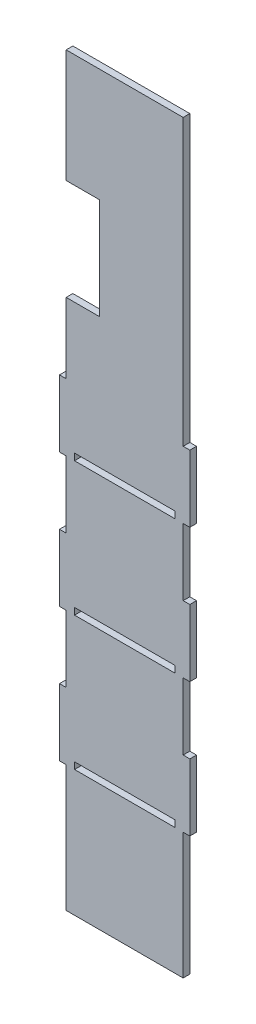
SolidWorks part; units mm, degrees
ref_plane "前视基准面" through (0, 0, 0) normal (0, 0, 1) x (1, 0, 0)
ref_plane "上视基准面" through (0, 0, 0) normal (0, 1, 0) x (1, 0, 0)
ref_plane "右视基准面" through (0, 0, 0) normal (1, 0, 0) x (0, 0, -1)
sketch "草图1" plane through (0, 0, 0) normal (0, 0, 1) x (1, 0, 0)
  line L38 (-8, 15.141) -> (-8, 49)
  line L39 (-8, 49) -> (27, 49)
  line L41 (-8, -15.141) -> (-8, -36.2215)
  line L42 (-8, -36.2215) -> (-10, -36.2215)
  line L43 (-10, -36.2215) -> (-10, -56.2215)
  line L44 (-10, -56.2215) -> (-8, -56.2215)
  line L45 (-8, -56.2215) -> (-8, -76.2215)
  line L46 (-8, -76.2215) -> (-10, -76.2215)
  line L47 (-10, -76.2215) -> (-10, -96.2215)
  line L48 (-10, -96.2215) -> (-8, -96.2215)
  line L49 (-8, -96.2215) -> (-8, -116.2215)
  line L52 (-8, -116.2215) -> (-10, -116.2215)
  line L53 (-10, -116.2215) -> (-10, -136.2215)
  line L54 (-10, -136.2215) -> (-8, -136.2215)
  line L55 (-8, -136.2215) -> (-8, -174)
  line L56 (-8, -174) -> (27, -174)
  line L58 (-8, -15.141) -> (2, -15.141)
  line L59 (2, -15.141) -> (2, 15.141)
  line L60 (2, 15.141) -> (-8, 15.141)
  line L61 (27, -136.2215) -> (27, -174)
  line L62 (29, -36.2215) -> (29, -56.2215)
  line L63 (29, -56.2215) -> (27, -56.2215)
  line L64 (27, -56.2215) -> (27, -76.2215)
  line L65 (27, -76.2215) -> (29, -76.2215)
  line L66 (29, -76.2215) -> (29, -96.2215)
  line L67 (29, -96.2215) -> (27, -96.2215)
  line L68 (27, -96.2215) -> (27, -116.2215)
  line L69 (29, -116.2215) -> (29, -136.2215)
  line L70 (29, -136.2215) -> (27, -136.2215)
  line L71 (27, -116.2215) -> (29, -116.2215)
  line L72 (27, 49) -> (27, -36.2215)
  line L73 (27, -36.2215) -> (29, -36.2215)
  line L83 (-5.5, -94.2215) -> (-5.5, -96.2215)
  line L84 (-5.5, -96.2215) -> (24.5, -96.2215)
  line L85 (24.5, -96.2215) -> (24.5, -94.2215)
  line L86 (24.5, -94.2215) -> (-5.5, -94.2215)
  line L87 (-5.5, -134.2215) -> (-5.5, -136.2215)
  line L88 (-5.5, -136.2215) -> (24.5, -136.2215)
  line L89 (24.5, -136.2215) -> (24.5, -134.2215)
  line L90 (24.5, -134.2215) -> (-5.5, -134.2215)
  line L91 (-5.5, -56.2215) -> (-5.5, -54.2215)
  line L92 (-5.5, -56.2215) -> (24.5, -56.2215)
  line L93 (-5.5, -54.2215) -> (24.5, -54.2215)
  line L94 (24.5, -54.2215) -> (24.5, -56.2215)
extrude "凸台-拉伸2" add sketch "草图1" along normal blind 2
